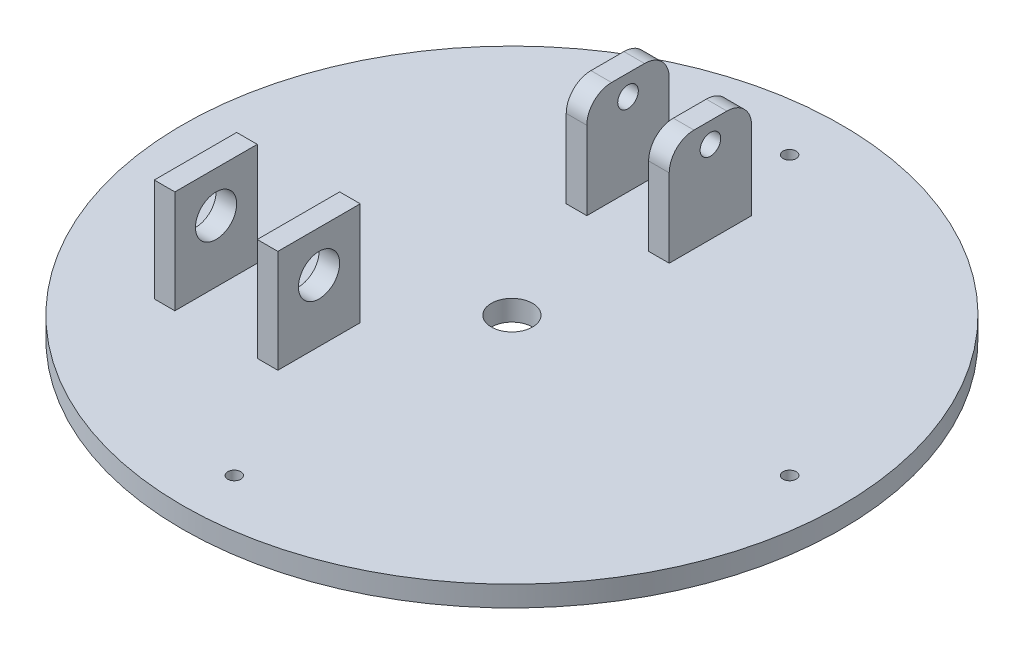
SolidWorks part; units mm, degrees
material "6061 Alloy"
ref_plane "Front Plane" through (0, 0, 0) normal (0, 0, 1) x (1, 0, 0)
ref_plane "Top Plane" through (0, 0, 0) normal (0, 1, 0) x (1, 0, 0)
ref_plane "Right Plane" through (0, 0, 0) normal (1, 0, 0) x (0, 0, -1)
sketch "Sketch1" plane through (0, 0, 0) normal (0, 1, 0) x (1, 0, 0)
  circle A0 centre (0, 0) radius 101.6
  dimension "D1" = 203.2
extrude "Boss-Extrude1" add sketch "Sketch1" along normal blind 6.35
sketch "Sketch2" plane through (0, 0, 0) normal (0, -1, 0) x (1, 0, 0)
  circle A0 centre (0, 0) radius 6.35
  dimension "D1" = 12.7
extrude "Cut-Extrude1" cut sketch "Sketch2" against normal through all
sketch "Sketch3" plane through (0, 6.35, 0) normal (0, 1, 0) x (1, 0, 0)
  line L0 (-53.1127, -38.1) -> (-27.7127, -38.1) construction
  line L1 (-59.4627, -25.4) -> (-53.1127, -25.4)
  line L2 (-59.4627, -25.4) -> (-59.4627, -50.8)
  line L3 (-59.4627, -50.8) -> (-53.1127, -50.8)
  line L4 (-53.1127, -25.4) -> (-53.1127, -50.8)
  line L5 (-27.7127, -25.4) -> (-21.3627, -25.4)
  line L6 (-27.7127, -25.4) -> (-27.7127, -50.8)
  line L7 (-27.7127, -50.8) -> (-21.3627, -50.8)
  line L8 (-21.3627, -25.4) -> (-21.3627, -50.8)
  point P10 (-40.4127, -38.1)
  dimension "D1" = 40.4127
  dimension "D2" = 6.35
  dimension "D3" = 38.1
  dimension "D4" = 25.4
  dimension "D5" = 25.4
extrude "Boss-Extrude2" add sketch "Sketch3" along normal blind 31.75
sketch "Sketch4" plane through (-21.3627, 0, 0) normal (1, 0, 0) x (0, 0, -1)
  line L0 (-38.1, 38.1) -> (-38.1, 25.4) construction
  line L1 (-50.8, 38.1) -> (-25.4, 38.1) construction
  circle A0 centre (-38.1, 25.4) radius 6.35
  dimension "D1" = 12.7
  dimension "D2" = 12.7
extrude "Cut-Extrude2" cut sketch "Sketch4" against normal up to surface (38.1 mm away) up to face at (-59.4627, 22.225, 38.1)
sketch "Sketch5" plane through (0, 6.35, 0) normal (0, 1, 0) x (1, 0, 0)
  line L0 (-15.0127, 50.8) -> (4.0373, 50.8) construction
  line L2 (-21.3627, 38.1) -> (-15.0127, 38.1)
  line L3 (-21.3627, 38.1) -> (-21.3627, 63.5)
  line L4 (-21.3627, 63.5) -> (-15.0127, 63.5)
  line L5 (-15.0127, 38.1) -> (-15.0127, 63.5)
  line L6 (4.0373, 63.5) -> (10.3873, 63.5)
  line L7 (4.0373, 63.5) -> (4.0373, 38.1)
  line L8 (4.0373, 38.1) -> (10.3873, 38.1)
  line L9 (10.3873, 63.5) -> (10.3873, 38.1)
  point P10 (-5.4877, 50.8)
  dimension "D1" = 25.4
  dimension "D2" = 6.35
  dimension "D3" = 19.05
  dimension "D4" = 34.925
  dimension "D5" = 88.9
extrude "Boss-Extrude3" add sketch "Sketch5" along normal blind 31.75
sketch "Sketch6" plane through (-21.3627, 0, 0) normal (-1, 0, 0) x (0, 0, 1)
  line L0 (-50.8, 38.1) -> (-50.8, 31.75) construction
  line L1 (-63.5, 38.1) -> (-38.1, 38.1) construction
  circle A0 centre (-50.8, 31.75) radius 3.175
  dimension "D1" = 6.35
  dimension "D2" = 6.35
extrude "Cut-Extrude3" cut sketch "Sketch6" against normal up to surface (31.75 mm away) up to face at (10.3873, 22.225, -50.8)
hole_wizard "#10-32 Tapped Hole1" positions "Sketch8" profile "Sketch7" tap size "#10-32" standard "ANSI Inch"
sketch "Sketch8" plane through (0, 0, 0) normal (0, -1, 0) x (-1, 0, 0)
  line L1 (85.5998, 0) -> (0, 85.5998)
  line L2 (85.5998, 0) -> (0, -85.5998)
  line L3 (0, 85.5998) -> (-85.5998, 0)
  line L4 (0, -85.5998) -> (-85.5998, 0)
  line L5 (85.5998, 0) -> (-85.5998, 0) construction
  line L6 (0, 85.5998) -> (0, -85.5998) construction
  point P252 (0, 0)
  point P331 (0, -85.5998)
  point P333 (-85.5998, 0)
  point P335 (0, 85.5998)
  point P337 (85.5998, 0)
  dimension "D1" = 121.0564
sketch "Sketch7" plane through (0, 0, 0) normal (1, 0, 0) x (0, 0, -1)
  line L0 (0, 0) -> (0, 13.2428)
  line L1 (0, 13.2428) -> (2.0193, 12.0294)
  line L2 (2.0193, 12.0294) -> (2.0193, 0)
  line L5 (2.0193, 0) -> (0, 0)
  line L10 (0, 13.2428) -> (-2.0193, 12.0294) construction
  line L11 (0, -6.35) -> (0, 107.95) construction
  dimension "Tap Drill Dia." = 4.0386
  dimension "Tap Drill Depth" = 12.0294
  dimension "Drill Angle" = 118
fillet "Fillet1" radius 7.62 4 edges at (7.2123, 38.1, -38.1) (-18.1877, 38.1, -38.1) (-18.1877, 38.1, -63.5) (7.2123, 38.1, -63.5)
